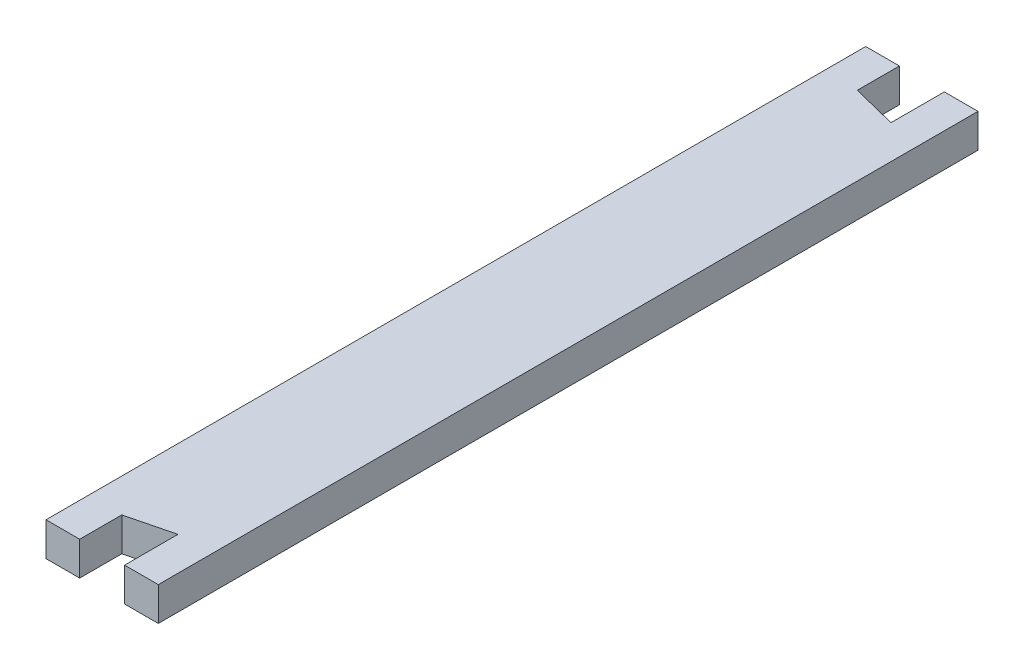
SolidWorks part; units mm, degrees
ref_plane "Front Plane" through (0, 0, 0) normal (0, 0, 1) x (1, 0, 0)
ref_plane "Top Plane" through (0, 0, 0) normal (0, 1, 0) x (1, 0, 0)
ref_plane "Right Plane" through (0, 0, 0) normal (1, 0, 0) x (0, 0, -1)
sketch "Sketch1" plane through (0, 0, 0) normal (0, 1, 0) x (1, 0, 0)
  line L0 (-450, 300) -> (-400, 300)
  line L1 (-400, 300) -> (-200, 250)
  line L2 (-200, 250) -> (200, 250) construction
  line L3 (200, 250) -> (600, 40) construction
  line L4 (600, 40) -> (1200, 40)
  line L5 (-450, -300) -> (-400, -300)
  line L6 (-400, -300) -> (-200, -250)
  line L7 (-200, -250) -> (200, -250) construction
  line L8 (200, -250) -> (600, -40) construction
  line L9 (600, -40) -> (1200, -40)
  line L10 (600, 40) -> (600, -40) construction
  line L11 (200, -250) -> (200, 250) construction
  line L12 (-200, 250) -> (-200, -250) construction
  line L13 (-400, -300) -> (-400, 300) construction
  line L14 (0, 0) -> (200, 0) construction
  line L15 (0, 250) -> (0, 0) construction
  line L16 (1200, 40) -> (1200, -40)
  line L17 (-450, 300) -> (-450, -300)
  line L18 (600, 0) -> (200, 0) construction
  line L19 (-450, 0) -> (-400, 0) construction
  line L20 (-400, 0) -> (-200, 0) construction
  line L21 (-200, 0) -> (0, 0) construction
  line L22 (-200, 250) -> (600, 40)
  line L23 (600, -40) -> (-200, -250)
  dimension "D1" = 600
  dimension "D2" = 200
  dimension "D3" = 50
  dimension "D4" = 400
  dimension "D5" = 500
  dimension "D6" = 80
  dimension "D7" = 600
  dimension "D8" = 400
extrude "Boss-Extrude1" add sketch "Sketch1" along normal blind 15
sketch "Sketch2" plane through (0, 0, 0) normal (0, 0, 1) x (1, 0, 0)
  line L0 (-450, 0) -> (-450, -40)
  line L1 (-450, -40) -> (-400, -40)
  line L2 (-400, -40) -> (-400, 0)
  line L3 (-400, 0) -> (-200, 0) construction
  line L4 (-400, 0) -> (-450, 0)
  line L5 (-440, -15) -> (-440, -40)
  line L6 (-410, -15) -> (-410, -40)
  line L7 (-425, 0) -> (-425, -15) construction
  circle A0 centre (-425, -15) radius 15
  dimension "D1" = 30
  dimension "D2" = 40
extrude "Boss-Extrude2" add sketch "Sketch2" along normal up to surface and the other way up to surface contours L4 L7 A0 L6 L1 L2 | L7 L4 L0 L1 L5 A0 up to face at (-425, 7.5, 300) other way up to face at (-425, 7.5, -300)
sketch "Sketch4" plane through (0, 0, 0) normal (0, 1, 0) x (1, 0, 0)
  line L0 (-450, 230) -> (-400, 230)
  line L1 (-450, 300) -> (-450, -300) construction
  line L2 (-400, 230) -> (-150, 167.5)
  line L3 (-150, 167.5) -> (-150, -167.5)
  line L4 (-150, -167.5) -> (-400, -230)
  line L5 (-400, -230) -> (-450, -230)
  line L6 (-400, 230) -> (-400, -230) construction
  line L7 (-200, 250) -> (-200, -250) construction
  line L9 (-200, 0) -> (-150, 0) construction
  line L10 (-400, -230) -> (-400, -300) construction
  line L11 (-400, -300) -> (-200, -250) construction
  line L12 (-450, 230) -> (-450, -230)
  line L14 (-200, 250) -> (-400, 300) construction
  line L15 (-100, 155) -> (-100, -155)
  line L16 (-100, -155) -> (520, 0)
  line L17 (520, 0) -> (-100, 155)
  line L18 (520, 0) -> (-100, 0) construction
  dimension "D1" = 460
  dimension "D2" = 300
  dimension "D3" = 50
extrude "Cut-Extrude2" cut sketch "Sketch4" against normal through all both and the other way through all
sketch "Sketch5" plane through (0, 0, 0) normal (1, 0, 0) x (0, 0, -1)
  line L0 (-300, 0) -> (-230, 0) construction
  line L1 (-285, 0) -> (-245, 0)
  line L2 (-285, 0) -> (-285, -40)
  line L3 (-285, -40) -> (-245, -40)
  line L4 (-245, 0) -> (-245, -40)
  line L5 (-300, -40) -> (-230, -40) construction
  line L6 (230, 0) -> (300, 0) construction
  line L7 (245, 0) -> (285, 0)
  line L8 (245, 0) -> (245, -40)
  line L9 (245, -40) -> (285, -40)
  line L10 (285, 0) -> (285, -40)
  line L11 (230, -40) -> (300, -40) construction
  line L12 (-300, 0) -> (-300, -40) construction
  line L13 (230, -40) -> (230, 0) construction
  line L14 (300, 0) -> (300, -40) construction
  dimension "D1" = 15
  dimension "D2" = 15
  dimension "D3" = 15
  dimension "D4" = 15
extrude "Cut-Extrude3" cut sketch "Sketch5" against normal through all
sketch "Sketch7" plane through (1200, 0, 0) normal (1, 0, 0) x (0, 0, -1)
  line L1 (-40, 15) -> (-87.5, 50)
  line L2 (-87.5, 50) -> (-87.5, 88.7)
  line L3 (-87.5, 88.7) -> (87.5, 88.7)
  line L4 (87.5, 88.7) -> (87.5, 50)
  line L5 (87.5, 50) -> (40, 15)
  line L7 (-40, 15) -> (40, 15)
  line L8 (-20, 50) -> (-20, 88.7)
  line L9 (87.5, 50) -> (-87.5, 50) construction
  line L10 (0, 88.7) -> (0, 50) construction
  line L11 (-20, 88.7) -> (20, 88.7)
  line L12 (0, 50) -> (0, 0) construction
  line L13 (20, 88.7) -> (20, 50)
  line L14 (-73, 88.7) -> (-63, 88.7)
  line L15 (-73, 88.7) -> (-73, 63.2)
  line L16 (-73, 63.2) -> (-63, 63.2)
  line L17 (-63, 88.7) -> (-63, 63.2)
  line L18 (48.5, 88.7) -> (58.5, 88.7)
  line L19 (48.5, 88.7) -> (48.5, 63.2)
  line L20 (48.5, 63.2) -> (58.5, 63.2)
  line L21 (58.5, 88.7) -> (58.5, 63.2)
  circle A0 centre (0, 50) radius 20
  dimension "D3" = 40
  dimension "D1" = 175
  dimension "D2" = 50
  dimension "D4" = 25.5
  dimension "D5" = 10
  dimension "D6" = 63
  dimension "D7" = 48.5
  dimension "D8" = 38.7
extrude "Boss-Extrude4" add sketch "Sketch7" against normal blind 75
sketch "Sketch8" plane through (0, 0, 0) normal (0, 0, 1) x (1, 0, 0)
  line L0 (1125, 88.7) -> (1200, 88.7) construction
  line L1 (1140, 88.7) -> (1185, 88.7)
  line L2 (1140, 88.7) -> (1140, 15)
  line L3 (1140, 15) -> (1185, 15)
  line L4 (1185, 88.7) -> (1185, 15)
  line L5 (1125, 15) -> (1200, 15) construction
  line L6 (1125, 50) -> (1125, 88.7) construction
  line L7 (1200, 50) -> (1200, 88.7) construction
  line L8 (1155, 88.7) -> (1170, 88.7) construction
  line L9 (1155, 88.7) -> (1170, 88.7)
  line L10 (1155, 88.7) -> (1155, 15)
  line L11 (1155, 15) -> (1170, 15)
  line L12 (1170, 88.7) -> (1170, 15)
  line L15 (1162.5, 50) -> (1162.5, 88.7) construction
  line L16 (1125, 50) -> (1200, 50) construction
  line L17 (1155, 88.7) -> (1170, 88.7) construction
  dimension "D1" = 15
  dimension "D2" = 15
  dimension "D3" = 15
extrude "Cut-Extrude4" cut sketch "Sketch8" against normal through all both and the other way through all contours L10 L1 L2 L3 | L1 L12 L3 L4
fillet "Fillet1" radius 5 53 edges at (1192.5, 50, 87.5) (1162.5, 50, 87.5) (1132.5, 50, 87.5) (1192.5, 50, -87.5) (1162.5, 50, -87.5) (1132.5, 50, -87.5) (1192.5, 88.7, -87.5) (1162.5, 88.7, -87.5) (1132.5, 88.7, -87.5) (1132.5, 88.7, -58.5) (1162.5, 88.7, -58.5) (1192.5, 88.7, -58.5) (1192.5, 88.7, -48.5) (1162.5, 88.7, -48.5) (1132.5, 88.7, -48.5) (1192.5, 88.7, -20) (1162.5, 88.7, -20) (1132.5, 88.7, -20) (1192.5, 88.7, 63) (1162.5, 88.7, 63) (1132.5, 88.7, 63) (1132.5, 88.7, 87.5) (1162.5, 88.7, 87.5) (1192.5, 88.7, 87.5) (1192.5, 88.7, 73) (1162.5, 88.7, 73) (1132.5, 88.7, 73) (1192.5, 88.7, 20) (1162.5, 88.7, 20) (1132.5, 88.7, 20) (600, 7.5, 40) (600, 7.5, -40) (520, 7.5, 0) (-440, -40, -292.5) (-440, -40, -237.5) (-400, -40, -292.5) (-400, -40, -237.5) (-450, -40, -237.5) (-410, -40, -237.5) (-450, -40, -292.5) (-410, -40, -292.5) (-150, 7.5, 167.5) (-100, 7.5, 155) (-150, 7.5, -167.5) (-100, 7.5, -155) (-450, -40, 237.5) (-410, -40, 237.5) (-440, -40, 237.5) (-400, -40, 237.5) (-450, -40, 292.5) (-440, -40, 292.5) (-400, -40, 292.5) (-410, -40, 292.5)
sketch "Sketch9" plane through (0, 0, 0) normal (0, 1, 0) x (1, 0, 0)
  line L35 (-450, -300) -> (-400, -300) construction
  line L36 (-425, -300) -> (-425, -285) construction
  line L37 (-450, 0) -> (0, 0) construction
  line L38 (-437.5, -300) -> (-412.5, -300)
  line L39 (-437.5, -300) -> (-437.5, -285)
  line L56 (1140, -40) -> (1140, -85.466) construction
  line L57 (1200, -40) -> (1185, -40)
  line L58 (1200, -40) -> (1200, -25)
  line L59 (1200, -25) -> (1185, -25)
  line L60 (1185, -40) -> (1185, -25)
  line L61 (1200, 40) -> (1185, 40)
  line L62 (1200, 40) -> (1200, 25)
  line L63 (1200, 25) -> (1185, 25)
  line L64 (1185, 40) -> (1185, 25)
  line L65 (1170, 40) -> (1155, 40)
  line L66 (1170, 40) -> (1170, 25)
  line L67 (1170, 25) -> (1155, 25)
  line L68 (1155, 40) -> (1155, 25)
  line L69 (1140, 40) -> (1125, 40)
  line L70 (1140, 40) -> (1140, 25)
  line L71 (1140, 25) -> (1125, 25)
  line L72 (1125, 40) -> (1125, 25)
  line L73 (1125, -40) -> (1140, -40)
  line L74 (1125, -40) -> (1125, -25)
  line L75 (1125, -25) -> (1140, -25)
  line L76 (1140, -40) -> (1140, -25)
  line L77 (1155, -40) -> (1170, -40)
  line L78 (1155, -40) -> (1155, -25)
  line L79 (1155, -25) -> (1170, -25)
  line L80 (1170, -40) -> (1170, -25)
  line L81 (600.6453, -40) -> (1200, -40) construction
  line L82 (1200, 40) -> (600.6453, 40) construction
  line L83 (1140, 40) -> (1125, 40) construction
  line L84 (1125, 85.466) -> (1125, 40) construction
  line L85 (1140, -25) -> (1155, -25) construction
  line L86 (1170, -25) -> (1185, -25) construction
  line L87 (1185, 25) -> (1170, 25) construction
  line L88 (1155, 25) -> (1140, 25) construction
  line L89 (-437.5, -285) -> (-412.5, -285)
  line L90 (-412.5, -300) -> (-412.5, -285)
  line L92 (-410, -230) -> (-440, -230) construction
  line L93 (-437.5, -230) -> (-412.5, -230)
  line L94 (-437.5, -230) -> (-437.5, -245)
  line L95 (-437.5, -245) -> (-412.5, -245)
  line L96 (-412.5, -230) -> (-412.5, -245)
  line L97 (-425, -245) -> (-400, -245) construction
  line L98 (-425, -285) -> (-425, -245) construction
  line L99 (-425, 285) -> (-425, 245) construction
  line L100 (-425, 300) -> (-425, 285) construction
  line L101 (-450, 300) -> (-400, 300) construction
  line L102 (-412.5, 230) -> (-412.5, 245)
  line L103 (-437.5, 245) -> (-412.5, 245)
  line L104 (-437.5, 230) -> (-437.5, 245)
  line L105 (-437.5, 230) -> (-412.5, 230)
  line L106 (-412.5, 300) -> (-412.5, 285)
  line L107 (-437.5, 285) -> (-412.5, 285)
  line L108 (-437.5, 300) -> (-437.5, 285)
  line L109 (-437.5, 300) -> (-412.5, 300)
  dimension "D1" = 15
  dimension "D2" = 25
  dimension "D3" = 15
extrude "Cut-Extrude5" cut sketch "Sketch9" against normal through all both and the other way through all
sketch "Sketch10" plane through (0, 0, 0) normal (0, 0, 1) x (1, 0, 0)
  line L1 (-450, 15) -> (1200, 15)
  line L2 (-450, 15) -> (-450, 0)
  line L3 (-450, 0) -> (1200, 0)
  line L4 (1200, 15) -> (1200, 0)
  line L5 (-450, 15) -> (-450, -35) construction
  line L6 (-486.0808, 110.0266) -> (1242.84, 110.0266)
  line L7 (-486.0808, 110.0266) -> (-486.0808, -68.8272)
  line L8 (-486.0808, -68.8272) -> (1242.84, -68.8272)
  line L9 (1242.84, 110.0266) -> (1242.84, -68.8272)
  dimension "D1" = 15
extrude "Cut-Extrude6" cut sketch "Sketch10" against normal through all both and the other way through all
sketch "Sketch11" plane through (0, 0, 0) normal (0, 1, 0) x (1, 0, 0)
  line L0 (-450, -315.625) -> (323.7848, -112.5065)
  line L1 (-200, -250) -> (599.3758, -40.1638) construction
  line L2 (-450, -315.625) -> (-450, -242.5)
  line L3 (-450, -230) -> (-450, -300) construction
  line L4 (-450, -242.5) -> (308.1542, -52.9615)
  line L5 (308.1542, -52.9615) -> (323.7848, -112.5065)
  line L6 (-400, -230) -> (-153.7873, -168.4468) construction
  line L7 (-450, -242.5) -> (-450, -230)
  line L8 (-450, -230) -> (-400, -230)
  line L9 (-150, -167.5) -> (-150, -182.5)
  line L10 (-150, -182.5) -> (-135, -182.5)
  line L11 (-135, -182.5) -> (-135, -163.75)
  line L12 (-100, -155) -> (-100, -182.5)
  line L13 (-100, -182.5) -> (-115, -182.5)
  line L14 (-115, -182.5) -> (-115, -158.75)
  line L15 (-100, 148.5961) -> (-100, -148.5961) construction
  line L16 (-150, -163.5961) -> (-150, 163.5961) construction
  line L17 (309.2763, -116.315) -> (305.4678, -101.8065)
  line L18 (-601.3695, -564.0724) -> (1251.3111, -564.0724)
  line L19 (-601.3695, -564.0724) -> (-601.3695, 511.8547)
  line L20 (-601.3695, 511.8547) -> (1251.3111, 511.8547)
  line L21 (1251.3111, -564.0724) -> (1251.3111, 511.8547)
  line L22 (305.4678, -101.8065) -> (319.9763, -97.998)
  line L23 (293.6011, -56.5997) -> (297.4095, -71.1082)
  line L24 (297.4095, -71.1082) -> (311.918, -67.2997)
  line L25 (305.4678, -101.8065) -> (297.4095, -71.1082) construction
  line L26 (-758.5651, 0) -> (1550.1652, 0) construction
  line L27 (-100, -155) -> (-100, 155)
  line L28 (-100, 0) -> (-150, 0)
  line L29 (-150, 167.5) -> (-150, -167.5)
  line L30 (-115, 182.5) -> (-115, 158.75)
  line L31 (-100, 182.5) -> (-115, 182.5)
  line L32 (-100, 155) -> (-100, 182.5)
  line L33 (-135, 182.5) -> (-135, 163.75)
  line L34 (-150, 182.5) -> (-135, 182.5)
  line L35 (-150, 167.5) -> (-150, 182.5)
  line L36 (-115, 158.75) -> (-135, 163.75)
  dimension "D1" = 800
  dimension "D2" = 15
  dimension "D3" = 15
  dimension "D4" = 15
  dimension "D5" = 15
extrude "Cut-Extrude7" cut sketch "Sketch11" along normal through all contours L18 L21 L20 L19 L36 L30 L31 L32 L27 L4 L5 L0 L2 L7 L8 L29 L35 L34 L33 | L24 L23 L4 L12 L13 L14 L11 L10 L9 L2 L0 L17 L22 L5 | L8 L7 L4 | L22 L17 L0 L5 | L23 L24 L5 L4
